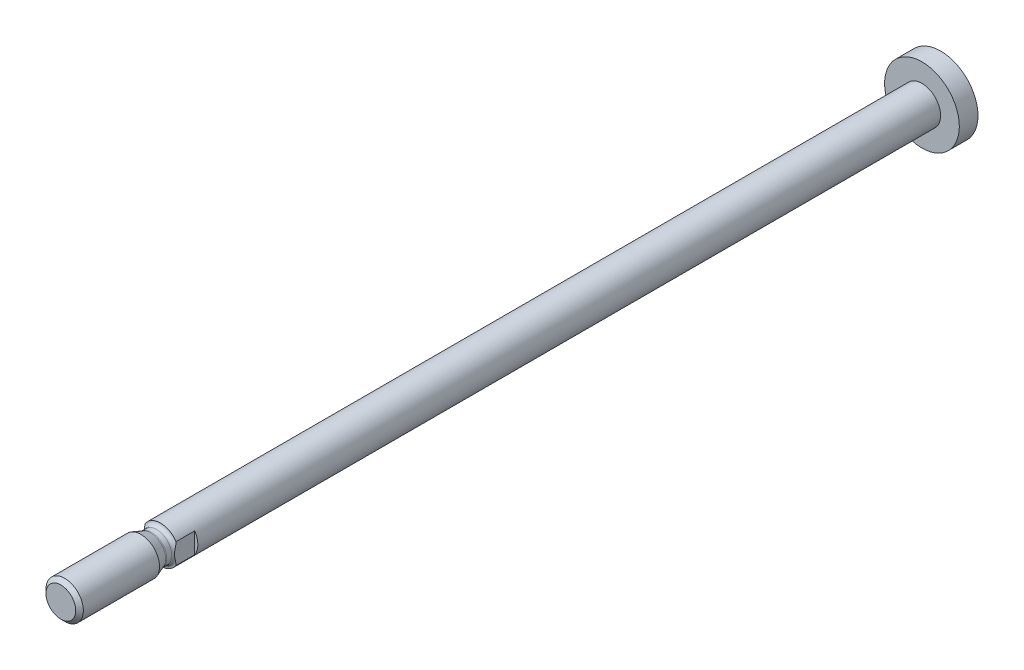
SolidWorks part; units mm, degrees
ref_plane "Front Plane" through (0, 0, 0) normal (0, 0, 1) x (1, 0, 0)
ref_plane "Top Plane" through (0, 0, 0) normal (0, 1, 0) x (1, 0, 0)
ref_plane "Right Plane" through (0, 0, 0) normal (1, 0, 0) x (0, 0, -1)
sketch "Sketch1" plane through (0, 0, 0) normal (1, 0, 0) x (0, 0, -1)
  line L0 (-5, 0) -> (-5, 3)
  line L1 (-5, 3) -> (117.3, 3)
  line L2 (117.3, 3) -> (117.3, 6)
  line L3 (117.3, 6) -> (120.3, 6)
  line L4 (120.3, 6) -> (120.3, 0)
  line L5 (120.3, 0) -> (-5, 0)
  line L6 (120.3, 0) -> (-5, 0) construction
revolve "Revolve1" add sketch "Sketch1" angle 360 about L6 reverse direction yes
sketch "Sketch2" plane through (0, 0, 0) normal (1, 0, 0) x (0, 0, -1)
  line L0 (-21, 0) -> (-21, 2.3865)
  line L1 (-21, 2.3865) -> (-20.3865, 3)
  line L2 (-20.3865, 3) -> (-8.1485, 3)
  line L3 (-8.1485, 3) -> (-6.5994, 2.4362)
  line L4 (-6.3942, 2.4) -> (-5.6, 2.4)
  line L5 (-5, 3) -> (-4, 3)
  line L6 (-4, 3) -> (-4, 0)
  line L7 (-4, 0) -> (-21, 0)
  line L8 (-4, 0) -> (-21, 0) construction
  arc A0 (-6.5994, 2.4362) -> (-6.3942, 2.4) centre (-6.3942, 3) ccw
  arc A1 (-5.6, 2.4) -> (-5, 3) centre (-5.6, 3) ccw
revolve "Revolve2" add sketch "Sketch2" angle 360 about L8 reverse direction yes
cosmetic thread "Cosmetic Thread1" parameters "D1"=12.8515, "D2"=4.773
ref_plane "Plane1" through (0, 0, 5) normal (0, 0, 1) x (1, 0, 0)
ref_plane "Plane2" through (0, 0, 2) normal (0, 0, 1) x (1, 0, 0)
sketch "Sketch3" plane through (0, 0, 2) normal (0, 0, 1) x (1, 0, 0)
  line L0 (-5, 10) -> (-5, -5)
  line L1 (-5, -5) -> (-2.5, -5)
  line L2 (-2.5, -5) -> (-2.5, 5)
  line L3 (-2.5, 5) -> (2.5, 5)
  line L4 (2.5, 5) -> (2.5, -5)
  line L5 (2.5, -5) -> (5, -5)
  line L6 (5, -5) -> (5, 10)
  line L7 (5, 10) -> (-5, 10)
extrude "Cut-Extrude1" cut sketch "Sketch3" along normal blind 4
ref_plane "Plane3" through (0, 0, -249) normal (0, 0, 1) x (1, 0, 0)
ref_plane "Plane4" through (0, 0, 16) normal (0, 0, 1) x (1, 0, 0)
ref_plane "Plane5" through (0, 0, 11.2) normal (0, 0, 1) x (1, 0, 0)
ref_plane "FDT_KSAUFSATZ XY" through (0, 0, 11.2) normal (0, 0, 1) x (1, 0, 0)
ref_plane "FDT_KSAUFSATZ XZ" through (0, 0, 0) normal (0, 1, 0) x (1, 0, 0)
ref_plane "FDT_KSAUFSATZ YZ" through (0, 0, 0) normal (-1, 0, 0) x (0, 0, 1)
ref_axis "FDT_KSAUFSATZ X" through (80.9, 0, 11.2) along (-1, 0, 0)
ref_axis "FDT_KSAUFSATZ Y" through (0, 50, 11.2) along (0, -1, 0)
ref_axis "FDT_KSAUFSATZ Z" through (0, 0, 80.9) along (0, 0, -1)
sketch3d "FDT_KSAUFSATZ"
  point P0 (0, 0, 11.2)
ref_plane "FDT_NUT XY" through (0, 0, 11.2) normal (0, 0, 1) x (1, 0, 0)
ref_plane "FDT_NUT XZ" through (0, 0, 0) normal (0, 1, 0) x (1, 0, 0)
ref_plane "FDT_NUT YZ" through (0, 0, 0) normal (-1, 0, 0) x (0, 0, 1)
ref_axis "FDT_NUT X" through (80.9, 0, 11.2) along (-1, 0, 0)
ref_axis "FDT_NUT Y" through (0, 50, 11.2) along (0, -1, 0)
ref_axis "FDT_NUT Z" through (0, 0, 80.9) along (0, 0, -1)
sketch3d "FDT_NUT"
  point P0 (0, 0, 11.2)
ref_plane "KS XY" through (0, 0, 0) normal (0, 0, -1) x (-1, 0, 0)
ref_plane "KS XZ" through (0, 0, 0) normal (0, 1, 0) x (1, 0, 0)
ref_plane "KS YZ" through (0, 0, 0) normal (1, 0, 0) x (0, 0, -1)
ref_axis "KS X" through (-80.9, 0, 0) along (1, 0, 0)
ref_axis "KS Y" through (0, 50, 0) along (0, -1, 0)
ref_axis "KS Z" through (0, 0, -80.9) along (0, 0, 1)
sketch3d "KS"
  point P0 (0, 0, 0)
ref_plane "NUT1 XY" through (0, 0, 16) normal (0, 0, 1) x (1, 0, 0)
ref_plane "NUT1 XZ" through (0, 0, 0) normal (0, -1, 0) x (-1, 0, 0)
ref_plane "NUT1 YZ" through (0, 0, 0) normal (1, 0, 0) x (0, 0, -1)
ref_axis "NUT1 X" through (-80.9, 0, 16) along (1, 0, 0)
ref_axis "NUT1 Y" through (0, -50, 16) along (0, 1, 0)
ref_axis "NUT1 Z" through (0, 0, 80.9) along (0, 0, -1)
sketch3d "NUT1"
  point P0 (0, 0, 16)
